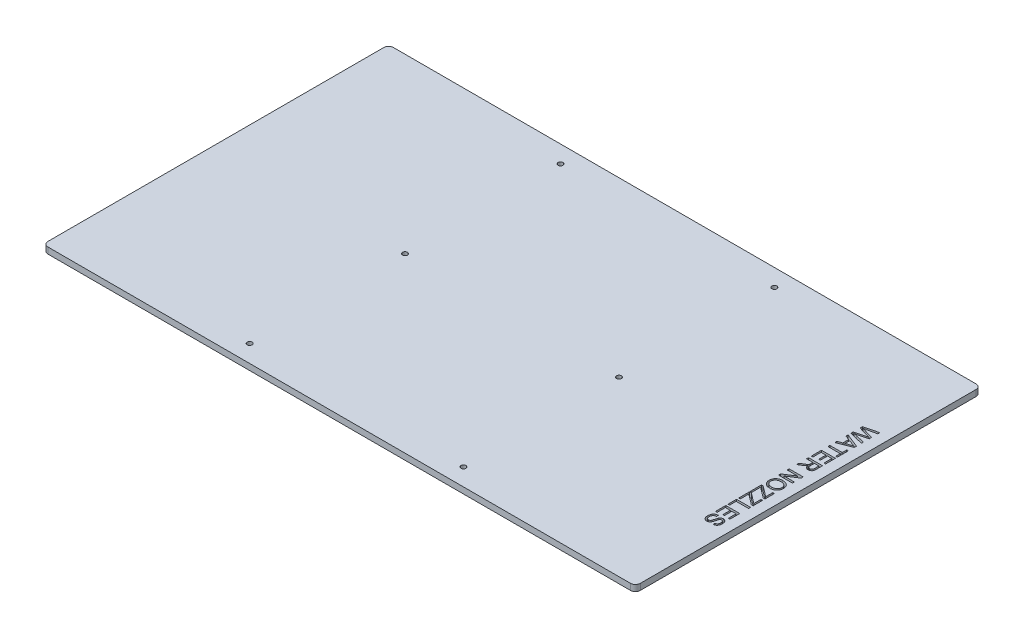
SolidWorks part; units mm, degrees
ref_plane "Front" through (0, 0, 0) normal (0, 0, 1) x (1, 0, 0)
ref_plane "Top" through (0, 0, 0) normal (0, 1, 0) x (1, 0, 0)
ref_plane "Right" through (0, 0, 0) normal (1, 0, 0) x (0, 0, -1)
sketch "Sketch1" plane through (0, 0, 0) normal (0, 1, 0) x (1, 0, 0)
  line L0 (139.7, 88.9) -> (139.7, -88.9) construction
  line L1 (-152.4, 88.9) -> (152.4, 88.9)
  line L2 (-152.4, 88.9) -> (-152.4, -88.9)
  line L3 (-152.4, -88.9) -> (152.4, -88.9)
  line L4 (152.4, 88.9) -> (152.4, -88.9)
  line L5 (-152.4, 88.9) -> (152.4, -88.9) construction
  line L6 (-152.4, -88.9) -> (152.4, 88.9) construction
  circle A0 centre (-55.0291, 80.01) radius 2.4574 construction
  circle A1 centre (-55.0291, 80.01) radius 2.4574 construction
  circle A2 centre (-55.0333, 0) radius 2.4574 construction
  circle A3 centre (-55.0333, 0) radius 2.4574 construction
  circle A4 centre (-55.0291, -80.01) radius 2.4574 construction
  circle A5 centre (-55.0291, -80.01) radius 2.4574 construction
  circle A6 centre (55.0291, -80.01) radius 2.4574 construction
  circle A7 centre (55.0291, -80.01) radius 2.4574 construction
  circle A8 centre (55.0333, 0) radius 2.4574 construction
  circle A9 centre (55.0333, 0) radius 2.4574 construction
  circle A10 centre (55.0291, 80.01) radius 2.4574 construction
  circle A11 centre (55.0291, 80.01) radius 2.4574 construction
  circle A12 centre (-55.0291, 80.01) radius 1.27
  circle A13 centre (-55.0333, 0) radius 1.27
  circle A14 centre (-55.0291, -80.01) radius 1.27
  circle A15 centre (55.0291, -80.01) radius 1.27
  circle A16 centre (55.0333, 0) radius 1.27
  circle A17 centre (55.0291, 80.01) radius 1.27
  point P0 (0, 0)
  dimension "D4" = 2.54
  dimension "D1" = 304.8
  dimension "D2" = 177.8
  dimension "D3" = 12.7
extrude "Boss-Extrude1" add sketch "Sketch1" along normal blind 3.175
sketch "Sketch2" plane through (0, 3.175, 0) normal (0, 1, 0) x (1, 0, 0)
  line L0 (139.7, 88.9) -> (139.7, -88.9) construction
  line L1 (152.4, 88.9) -> (-152.4, 88.9) construction
  line L2 (-152.4, -88.9) -> (152.4, -88.9) construction
  line L3 (152.4, -88.9) -> (152.4, 88.9) construction
  text T0 "WATER NOZZLES" font "Arial" height in points 28
  dimension "D1" = 12.7
extrude "Cut-Extrude1" cut sketch "Sketch2" against normal blind 2.54
fillet "Fillet1" radius 2.54 4 edges at (152.4, 1.5875, -88.9) (152.4, 1.5875, 88.9) (-152.4, 1.5875, 88.9) (-152.4, 1.5875, -88.9)
